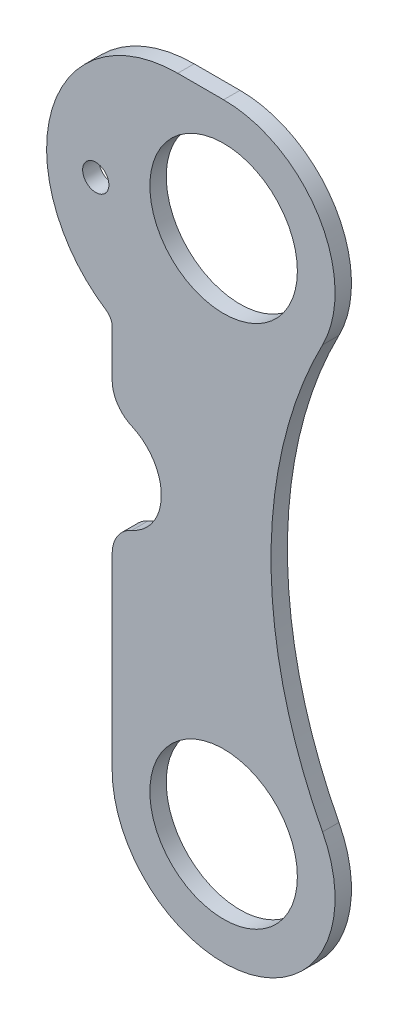
SolidWorks part; units mm, degrees
material "6061 Alloy"
ref_plane "Front Plane" through (0, 0, 0) normal (0, 0, 1) x (1, 0, 0)
ref_plane "Top Plane" through (0, 0, 0) normal (0, 1, 0) x (1, 0, 0)
ref_plane "Right Plane" through (0, 0, 0) normal (1, 0, 0) x (0, 0, -1)
sketch "Sketch1" plane through (0, 0, 0) normal (0, 0, 1) x (1, 0, 0)
  line L0 (0, 0) -> (0, -101.6) construction
  line L1 (21.59, -120.5575) -> (-21.59, -120.5575) construction
  line L2 (-8.89, 25.4) -> (8.89, 25.4)
  line L3 (-21.59, 12.7) -> (-21.59, -117.7751)
  line L5 (21.59, 12.7) -> (21.59, -117.7751)
  line L9 (-23.3829, -122.6853) -> (-33.2033, -134.3394)
  line L10 (-36.322, 25.4) -> (20.828, 25.4) construction
  line L11 (-36.322, 25.4) -> (-36.322, -203.2) construction
  line L12 (-36.322, -203.2) -> (20.828, -203.2) construction
  line L13 (20.828, 25.4) -> (20.828, -203.2) construction
  line L15 (-7.9527, -155.6168) -> (19.7971, -122.6853)
  line L16 (-32.4392, -143.2871) -> (-16.9004, -156.3809)
  circle A0 centre (0, 0) radius 38.1 construction
  circle A1 centre (0, -101.6) radius 38.1 construction
  circle A2 centre (0, 0) radius 14.2875
  circle A3 centre (0, -101.6) radius 14.2875
  arc A6 (8.89, 25.4) -> (21.59, 12.7) centre (8.89, 12.7) cw
  arc A7 (-8.89, 25.4) -> (-21.59, 12.7) centre (-8.89, 12.7) ccw
  circle A10 centre (-18.5321, -142.5501) radius 2.54
  arc A13 (-23.3829, -122.6853) -> (-21.59, -117.7751) centre (-29.21, -117.7751) ccw
  arc A14 (19.7971, -122.6853) -> (21.59, -117.7751) centre (13.97, -117.7751) ccw
  arc A15 (-16.9004, -156.3809) -> (-7.9527, -155.6168) centre (-12.8086, -151.525) ccw
  arc A16 (-33.2033, -134.3394) -> (-32.4392, -143.2871) centre (-28.3474, -138.4312) ccw
  point P13 (-192.705, 39.2708)
  point P20 (21.59, 25.4)
  point P23 (-21.59, 25.4)
  point P31 (-36.322, -138.0404)
  dimension "D2" = 76.2
  dimension "D3" = 76.2
  dimension "D4" = 28.575
  dimension "D5" = 28.575
  dimension "D10" = 228.6
  dimension "D11" = 36.322
  dimension "D13" = 5.08
  dimension "D19" = 6.35
  dimension "D20" = 7.62
  dimension "D21" = 12.7
  dimension "D1" = 101.6
  dimension "D6" = 43.18
  dimension "D7" = 21.59
  dimension "D8" = 25.4
  dimension "D9" = 57.15
  dimension "D12" = 25.4
  dimension "D14" = 33.02
  dimension "D15" = 16.51
  dimension "D16" = 21.59
  dimension "D17" = 9.525
  dimension "D18" = 18.9575
extrude "Boss-Extrude1" add sketch "Sketch1" along normal blind 3.175
sketch "Sketch2" plane through (0, 0, 0) normal (0, 0, 1) x (1, 0, 0)
  line L0 (-21.59, -41.275) -> (-21.59, -60.325)
  line L1 (0, 0) -> (0, -101.6) construction
  line L4 (21.59, -117.7751) -> (21.59, 12.7) construction
  line L5 (-21.59, -50.8) -> (97.79, -50.8) construction
  line L6 (-21.59, 12.7) -> (-21.59, -117.7751) construction
  line L7 (0, 0) -> (-39.9512, 0) construction
  line L9 (16.51, -115.5122) -> (-17.5013, -155.8745)
  line L10 (-32.4392, -143.2871) -> (-16.9004, -156.3809) construction
  line L11 (-7.9527, -155.6168) -> (19.7971, -122.6853) construction
  line L13 (27.94, -121.6567) -> (-7.6203, -163.8572)
  line L14 (-7.6203, -163.8572) -> (-17.5013, -155.8745)
  line L15 (27.94, -121.6567) -> (27.94, 0)
  line L16 (27.94, 0) -> (21.59, 0)
  arc A1 (19.1591, -91.6472) -> (19.1591, -9.9528) centre (97.79, -50.8) cw
  arc A2 (-21.59, -60.325) -> (-21.59, -41.275) centre (-21.59, -50.8) ccw
  arc A3 (21.59, 0) -> (19.1591, -9.9528) centre (0, 0) cw
  arc A4 (21.59, -101.6) -> (19.1591, -91.6472) centre (0, -101.6) ccw
  arc A5 (21.59, -101.6) -> (16.51, -115.5122) centre (0, -101.6) cw
  dimension "D2" = 12.7
  dimension "D3" = 50.8
  dimension "D4" = 6.35
  dimension "D1" = 76.2
  dimension "D5" = 19.05
extrude "Cut-Extrude1" cut sketch "Sketch2" along normal through all contours A1 A3 L16 L15 L13 L14 L9 A5 A4 | L0 A2
sketch "Sketch3" plane through (0, 0, 3.175) normal (0, 0, 1) x (1, 0, 0)
  line L0 (-27.3514, -127.3948) -> (-36.0255, -137.6886)
  line L3 (-27.3514, -127.3948) -> (-7.5576, -144.074)
  line L4 (-23.3829, -122.6853) -> (-33.2033, -134.3394) construction
  line L5 (16.51, -115.5122) -> (-17.5013, -155.8745) construction
  line L7 (-35.4064, -144.9387) -> (-24.4031, -154.2106)
  line L8 (-23.3829, -122.6853) -> (-33.2033, -134.3394) construction
  line L9 (-7.5576, -144.074) -> (-15.4554, -153.4465)
  line L10 (-32.4392, -143.2871) -> (-17.5013, -155.8745) construction
  circle A2 centre (-18.5321, -142.5501) radius 2.54
  circle A3 centre (-18.5321, -142.5501) radius 2.54 construction
  arc A5 (-36.0255, -137.6886) -> (-35.4064, -144.9387) centre (-32.0909, -141.0041) ccw
  arc A6 (-24.4031, -154.2106) -> (-15.4554, -153.4465) centre (-20.3113, -149.3547) ccw
  dimension "D2" = 6.35
  dimension "D3" = 5.1453
  dimension "D1" = 3.175
fillet "Fillet3" radius 6.35 2 edges at (-21.59, -41.275, 1.5875) (-21.59, -60.325, 1.5875)
extrude "Boss-Extrude3" add sketch "Sketch3" against normal blind 3.175
sketch "Sketch6" plane through (0, 0, 3.175) normal (0, 0, 1) x (1, 0, 0)
  line L0 (-35.4064, -144.9387) -> (-63.6204, -121.1641)
  line L1 (-63.6204, -121.1641) -> (-51.345, -106.5965)
  line L2 (-51.345, -106.5965) -> (-27.0656, -127.0555)
  line L4 (-35.4064, -144.9387) -> (-24.4031, -154.2106) construction
  line L5 (-23.3829, -122.6853) -> (-36.0255, -137.6886) construction
  line L6 (-35.4064, -144.9387) -> (-27.0656, -127.0555)
  circle A0 centre (-52.6268, -117.9721) radius 2.54
  dimension "D4" = 5.08
  dimension "D1" = 31.75
  dimension "D2" = 9.525
  dimension "1" = 19.05
  dimension "D3" = 6.35
extrude "Boss-Extrude4" add sketch "Sketch6" against normal blind 3.175
fillet "Fillet2" radius 6.35 3 edges at (-63.6204, -121.1641, 1.5875) (-51.345, -106.5965, 1.5875) (-27.0656, -127.0555, 1.5875)
sketch "Sketch7" plane through (0, 0, 3.175) normal (0, 0, 1) x (1, 0, 0)
  line L0 (-21.59, 12.7) -> (-21.59, -36.2503) construction
  line L1 (21.59, 0) -> (21.59, 12.7) construction
  line L2 (-21.59, 0) -> (21.59, 0) construction
  line L3 (-21.59, 0) -> (-21.59, 31.75)
  line L4 (-21.59, 31.75) -> (21.59, 31.75)
  line L5 (21.59, 31.75) -> (21.59, 0)
  line L6 (8.89, 25.4) -> (-8.89, 25.4) construction
  arc A0 (-21.59, 0) -> (21.59, 0) centre (0, 0) cw
  dimension "D1" = 6.35
extrude "Cut-Extrude2" cut sketch "Sketch7" against normal through all
sketch "Sketch10" plane through (0, 0, 3.175) normal (0, 0, 1) x (1, 0, 0)
  line L0 (16.51, -115.5122) -> (-17.5013, -155.8745) construction
  line L1 (-18.1519, -155.3263) -> (-17.3615, -157.512)
  line L2 (-17.3615, -157.512) -> (-14.3757, -156.4323)
  line L3 (-14.3757, -156.4323) -> (-15.4554, -153.4465)
  line L5 (-18.1519, -155.3263) -> (-17.5013, -155.8745) construction
  circle A0 centre (-20.3113, -149.3547) radius 6.35 construction
  arc A1 (-24.4031, -154.2106) -> (-18.1519, -155.3263) centre (-20.3113, -149.3547) ccw construction
  arc A2 (-18.1519, -155.3263) -> (-15.4554, -153.4465) centre (-20.3113, -149.3547) ccw
  dimension "D1" = 3.175
  dimension "D2" = 30
extrude "Cut-Extrude3" cut sketch "Sketch10" against normal through all
sketch "Sketch12" plane through (0, 0, 3.175) normal (0, 0, 1) x (1, 0, 0)
  line L0 (-21.59, -65.3497) -> (-21.59, -117.7751) construction
  line L1 (-21.59, -101.6) -> (-72.39, -101.6)
  line L2 (-72.39, -101.6) -> (-72.39, -165.1)
  line L3 (-72.39, -165.1) -> (16.51, -165.1)
  line L4 (16.51, -165.1) -> (16.51, -115.5122)
  arc A2 (16.51, -115.5122) -> (-21.59, -101.6) centre (0, -101.6) cw
  dimension "D1" = 63.5
  dimension "D2" = 88.9
extrude "Cut-Extrude4" cut sketch "Sketch12" against normal through all
sketch "Sketch15" plane through (0, 0, 3.175) normal (0, 0, 1) x (1, 0, 0)
  line L0 (-21.59, 0) -> (-21.59, -36.2503) construction
  line L5 (-21.59, -29.21) -> (-21.59, 0)
  line L7 (0, 21.59) -> (-16.6076, 6.9565)
  line L8 (-16.6076, 6.9565) -> (-12.5785, -28.9408)
  line L9 (-8.89, 21.59) -> (0, 21.59)
  arc A0 (-12.5785, -28.9408) -> (-34.29, -3.81) centre (-8.89, -3.81) cw
  arc A1 (-8.89, 21.59) -> (-34.29, -3.81) centre (-8.89, -3.81) ccw
  circle A2 centre (-24.765, -3.81) radius 2.54
  arc A3 (19.1591, -9.9528) -> (-21.59, 0) centre (0, 0) ccw construction
  arc M10 (19.1591, -9.9528) -> (-21.59, 0) centre (0, 0) ccw
  line M11 (-21.59, 0) -> (-21.59, -36.2503)
  dimension "D1" = 12.7
  dimension "D4" = 3.175
  dimension "D3" = 5.08
  dimension "D2" = 25.4
extrude "Boss-Extrude8" add sketch "Sketch15" against normal blind 3.175 contours L9 A1 A0 A2 M11 M10 region at (-24.9677, -0.0937, 3.175)
fillet "Fillet4" radius 2.54 1 edges at (-21.59, -25.807, 1.5875)
